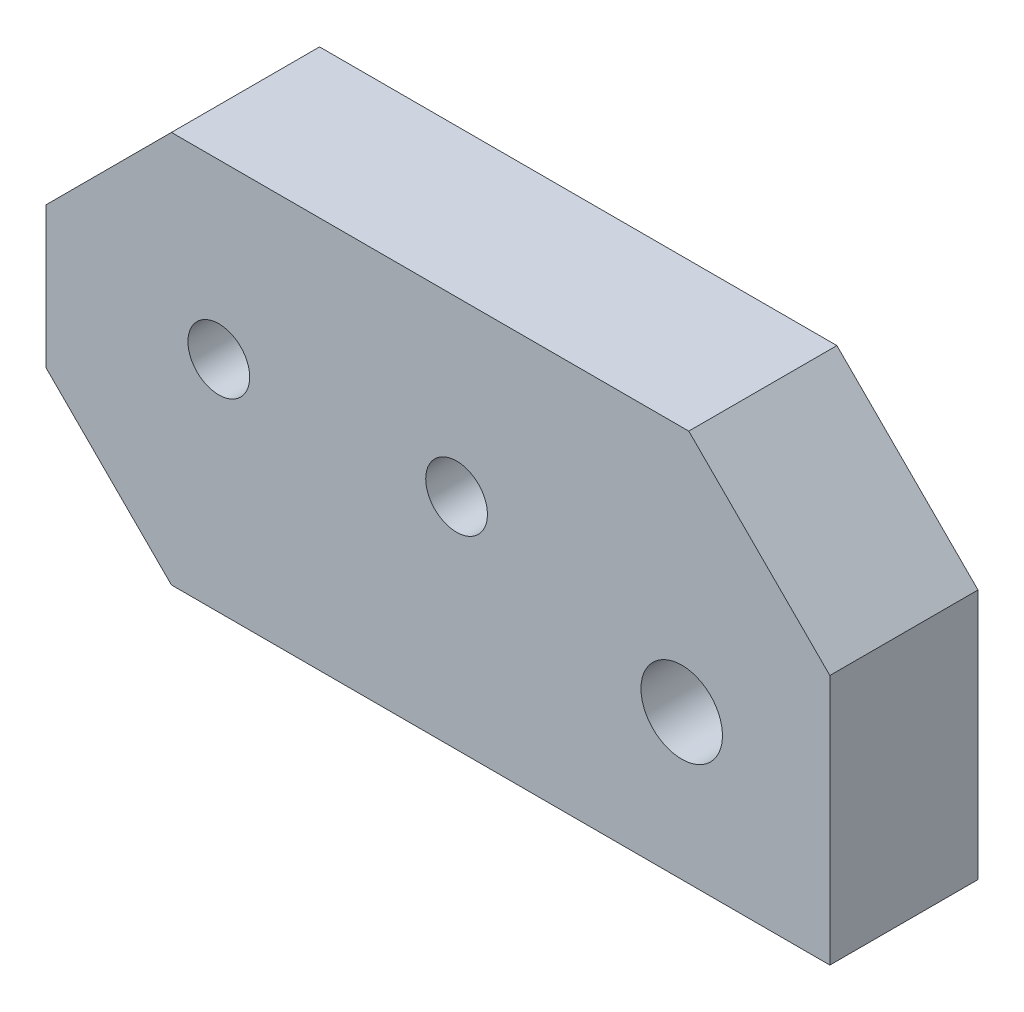
SolidWorks part; units mm, degrees
ref_plane "Front Plane" through (0, 0, 0) normal (0, 0, 1) x (1, 0, 0)
ref_plane "Top Plane" through (0, 0, 0) normal (0, 1, 0) x (1, 0, 0)
ref_plane "Right Plane" through (0, 0, 0) normal (1, 0, 0) x (0, 0, -1)
sketch "Sketch2" plane through (0, 0, 0) normal (0, 0, 1) x (1, 0, 0)
  line L0 (-21.59, 15.875) -> (-31.75, 15.875) construction
  line L1 (31.75, -15.875) -> (-21.59, -15.875)
  line L2 (31.75, -15.875) -> (31.75, 4.445)
  line L3 (20.32, 15.875) -> (-21.59, 15.875)
  line L5 (31.75, -15.875) -> (-31.75, 15.875) construction
  line L6 (31.75, 15.875) -> (-31.75, -15.875) construction
  line L7 (-31.75, 5.715) -> (-21.59, 15.875)
  line L8 (-31.75, -5.715) -> (-21.59, -15.875)
  line L9 (-31.75, 0) -> (0, 0) construction
  line L10 (-21.59, -15.875) -> (-31.75, -15.875) construction
  line L12 (-31.75, 15.875) -> (-31.75, 5.715) construction
  line L13 (-31.75, 5.715) -> (-31.75, -5.715)
  line L14 (-31.75, -5.715) -> (-31.75, -15.875) construction
  line L15 (20.32, 15.875) -> (31.75, 4.445)
  line L16 (31.75, 15.875) -> (20.32, 15.875) construction
  line L17 (31.75, 4.445) -> (31.75, 15.875) construction
  point P0 (0, 0)
  dimension "D1" = 63.5
  dimension "D2" = 31.75
  dimension "D3" = 45
  dimension "D4" = 11.43
  dimension "D5" = 45
  dimension "D6" = 11.43
  dimension "D7" = 10.16
extrude "Boss-Extrude1" add sketch "Sketch2" along normal mid plane 12
hole_wizard "M6x1.0 Tapped Hole1" positions "Sketch5" profile "Sketch4" tap size "M6x1.0" standard "ANSI Metric" end condition through all
sketch "Sketch5" plane through (0, 0, -6) normal (0, 0, -1) x (-1, 0, 0)
  line L1 (31.75, 5.715) -> (31.75, -5.715) construction
  line L2 (-20.32, 15.875) -> (21.59, 15.875) construction
  line L3 (21.59, 15.875) -> (31.75, 5.715) construction
  point P0 (17.75, 1.875)
  point P2 (-1.51, 1.875)
  dimension "D1" = 19.26
  dimension "D2" = 14
  dimension "D3" = 14
  dimension "D4" = 12.6148
sketch "Sketch4" plane through (-17.75, 1.875, -6) normal (1, 0, 0) x (0, 1, 0)
  line L0 (0, 0) -> (0, 12)
  line L1 (0, 12) -> (2.5, 12)
  line L2 (2.5, 12) -> (2.5, 0)
  line L5 (2.5, 0) -> (0, 0)
  line L11 (0, -6.35) -> (0, 107.95) construction
  dimension "Thru Tap Drill Dia." = 5
  dimension "Thru Tap Drill Depth" = 12
cosmetic thread "Hole Thread1"
cosmetic thread "Hole Thread2"
hole_wizard "M6 Clearance Hole1" positions "Sketch8" profile "Sketch7" hole size "M6" standard "ANSI Metric" end condition through all
sketch "Sketch8" plane through (0, 0, -6) normal (0, 0, -1) x (-1, 0, 0)
  line L1 (21.59, -15.875) -> (-31.75, -15.875) construction
  line L2 (-31.75, -15.875) -> (-31.75, 4.445) construction
  point P0 (-19.7484, -4.125)
  dimension "D1" = 11.75
  dimension "D2" = 12.0016
sketch "Sketch7" plane through (19.7484, -4.125, -6) normal (1, 0, 0) x (0, 1, 0)
  line L0 (0, 0) -> (0, 12)
  line L1 (0, 12) -> (3.3, 12)
  line L2 (3.3, 12) -> (3.3, 0)
  line L5 (3.3, 0) -> (0, 0)
  line L11 (0, -6.35) -> (0, 107.95) construction
  dimension "Thru Hole Dia." = 6.6
  dimension "Thru Hole Depth" = 12
